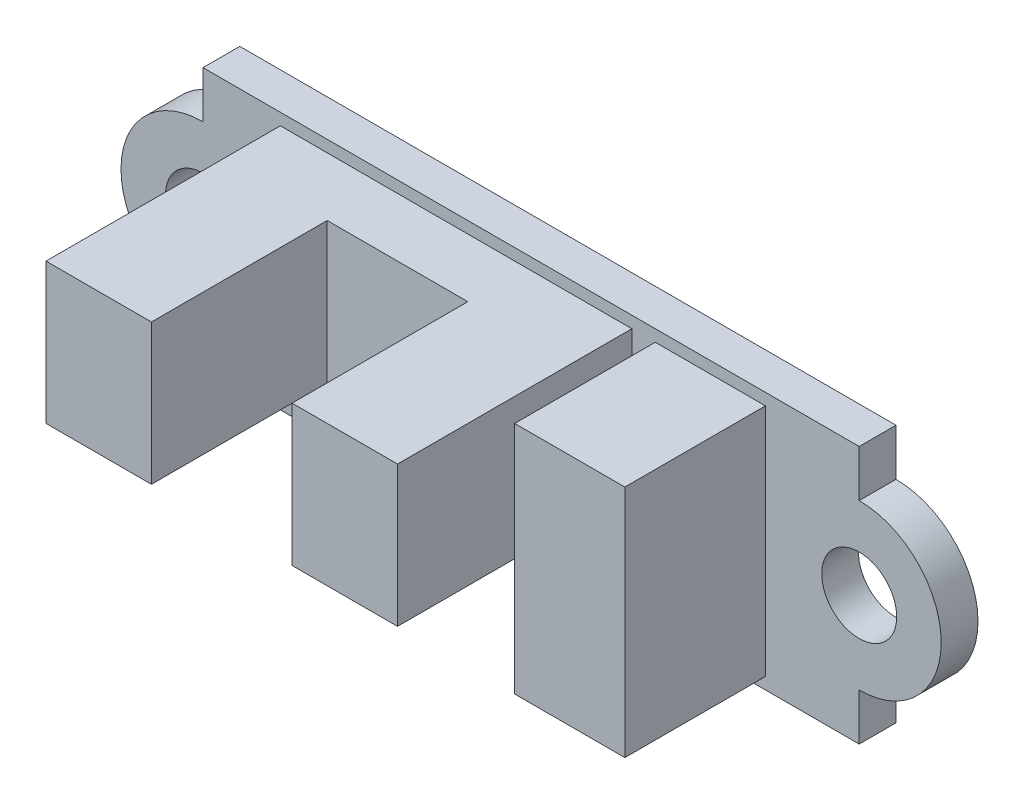
SolidWorks part; units mm, degrees
ref_plane "Top" through (0, 0, 0) normal (0, 0, 1) x (1, 0, 0)
ref_plane "Front" through (0, 0, 0) normal (0, 1, 0) x (1, 0, 0)
ref_plane "Right" through (0, 0, 0) normal (1, 0, 0) x (0, 0, -1)
sketch "Sketch1" plane through (0, 0, 0) normal (0, 0, 1) x (1, 0, 0)
  line L0 (-14, 3.5) -> (-14, 5.5)
  line L1 (-14, -5.5) -> (14, -5.5)
  line L2 (-14, -5.5) -> (-14, -3.5)
  line L3 (-14, 5.5) -> (14, 5.5)
  line L4 (14, -5.5) -> (14, -3.5)
  line L5 (-14, -5.5) -> (14, 5.5) construction
  line L6 (-14, 5.5) -> (14, -5.5) construction
  line L7 (14, 3.5) -> (14, 5.5)
  circle A0 centre (-14, 0) radius 1.6
  arc A1 (-14, 3.5) -> (-14, -3.5) centre (-14, 0) ccw
  circle A2 centre (14, 0) radius 1.6
  arc A3 (14, -3.5) -> (14, 3.5) centre (14, 0) ccw
  point P0 (0, 0)
  dimension "D3" = 3.2
  dimension "D4" = 7
  dimension "D5" = 5.5
  dimension "D1" = 11
  dimension "D2" = 28
extrude "PCB" add sketch "Sketch1" against normal blind 1.57
sketch "Sketch2" plane through (0, 0, 0) normal (0, 0, 1) x (1, 0, 0)
  line L0 (-6.2, 5) -> (-6.2, -1)
  line L1 (-17.5, -5.5) -> (17.5, -5.5) construction
  line L2 (-17.5, -5.5) -> (-17.5, 5.5) construction
  line L3 (-17.5, 5.5) -> (17.5, 5.5) construction
  line L4 (17.5, -5.5) -> (17.5, 5.5) construction
  line L5 (-17.5, -5.5) -> (17.5, 5.5) construction
  line L6 (-17.5, 5.5) -> (17.5, -5.5) construction
  line L7 (-10.7, 5) -> (4.3, 5)
  line L8 (-10.7, 5) -> (-10.7, -1)
  line L9 (-10.7, -1) -> (4.3, -1)
  line L10 (4.3, 5) -> (4.3, -1)
  line L11 (-0.2, 5) -> (-0.2, -1)
  line L12 (14, 0) -> (17.5, 0) construction
  line L13 (5.3, 5) -> (10, 5)
  line L14 (5.3, 5) -> (5.3, -5)
  line L15 (5.3, -5) -> (10, -5)
  line L16 (10, 5) -> (10, -5)
  line L17 (10.5, 5.5) -> (10.5, -5.5) construction
  circle A0 centre (14, 0) radius 3.5 construction
  point P0 (0, 0)
  dimension "D11" = 7
  dimension "D1" = 11
  dimension "D2" = 35
  dimension "D3" = 11.3
  dimension "D4" = 4.5
  dimension "D5" = 6
  dimension "D6" = 4.5
  dimension "D7" = 0.5
  dimension "D8" = 6
  dimension "D9" = 0.5
  dimension "D10" = 1
  dimension "D12" = 0.5
extrude "Optical Sensor Base" add sketch "Sketch2" along normal blind 2.5 separate body contours L11 L7 L0 L9 region at (-3.2, 2, 0)
extrude "Optical Sensor Sides" add sketch "Sketch2<3>" along normal blind 10 contours L8 L9 L0 L7 | L7 L11 L9 L10 region at (-8.45, 2, 0) region at (2.05, 2, 0)
sketch "Sketch2<3>" plane through (0, 0, 0) normal (0, 0, 1) x (1, 0, 0) same geometry as "Sketch2"
extrude "Connector" add sketch "Sketch2<4>" along normal blind 6 contours L16 L13 L14 L15 region at (7.65, 0, 0)
sketch "Sketch2<4>" plane through (0, 0, 0) normal (0, 0, 1) x (1, 0, 0) same geometry as "Sketch2"
equation "\"M2x0.4_Close_Hole\"= 2.2"
equation "\"M2.5x0.45_Close_Hole\"= 2.7"
equation "\"M3x0.5_Close_Hole\"= 3.2"
equation "\"M4x0.7_Close_Hole\"= 4.3"
equation "\"M5x0.8_Close_Hole\"= 5.3"
equation "\"M6x1_Close_Hole\"= 6.3"
equation "\"M7x1_Close_Hole\"= 7.4"
equation "\"M8x1.25_Close_Hole\"= 8.4"
equation "\"M2x0.4_Tap_Hole_75\"= 1.6"
equation "\"M3x0.5_Tap_Hole_75\"= 2.5"
equation "\"M4x0.7_Tap_Hole_75\"= 3.3"
equation "\"M5x0.8_Tap_Hole_75\"= 4.2"
equation "\"M6x1_Tap_Hole_75\"= 5"
equation "\"M7x1_Tap_Hole_75\"= 6"
equation "\"M8x1.25_Tap_Hole_75\"= 6.8"
